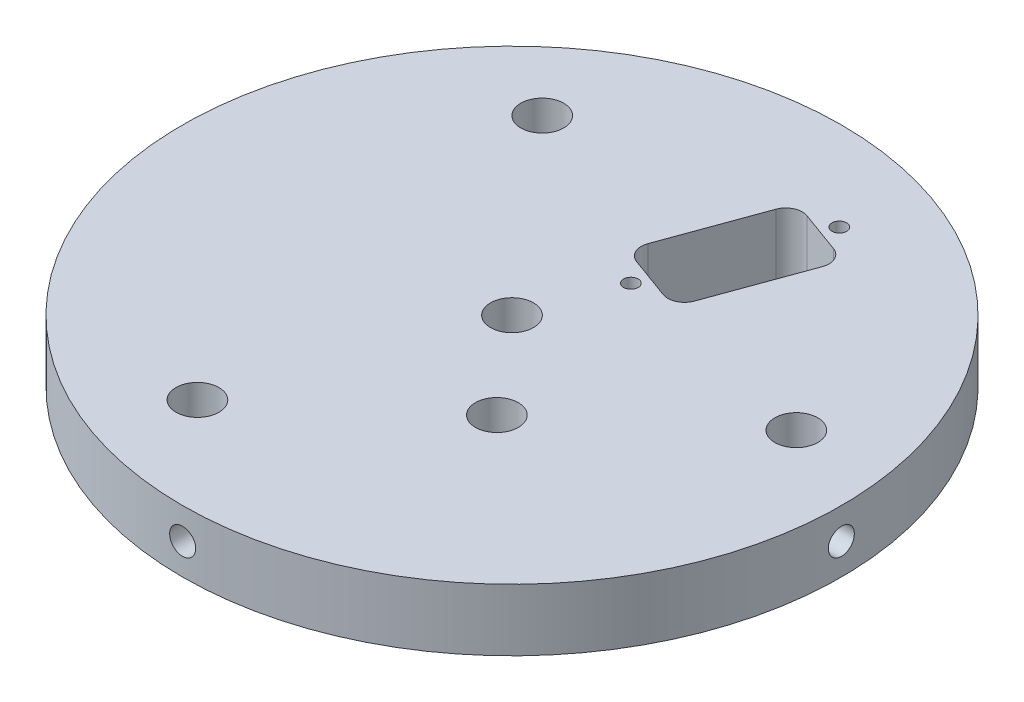
SolidWorks part; units mm, degrees
material "6061-T6 (SS)"
ref_plane "Front Plane" through (0, 0, 0) normal (0, 0, 1) x (1, 0, 0)
ref_plane "Top Plane" through (0, 0, 0) normal (0, 1, 0) x (1, 0, 0)
ref_plane "Right Plane" through (0, 0, 0) normal (1, 0, 0) x (0, 0, -1)
sketch "Sketch1" plane through (0, 0, 0) normal (0, 1, 0) x (1, 0, 0)
  line L0 (0, 0) -> (-50.3682, 60.0265)
  line L1 (0, 0) -> (50.3682, 60.0265)
  line L2 (0, 0) -> (0, 72.1431) construction
  circle A0 centre (0, 0) radius 78.359
  circle A1 centre (0, 0) radius 76.1746
  circle A2 centre (0, 0) radius 76.1746
  dimension "D1" = 156.718
  dimension "D2" = 152.3492
  dimension "D3" = 152.3492
  dimension "D4" = 80
extrude "Boss-Extrude1" add sketch "Sketch1" along normal blind 25.4 contours L2 A2 L1 A0 | L2 A1 L1 A2 | L2 A2 L1 A1 | L2 A0 L1 A2 | A2 L2 A1 L0 | A0 L2 A2 L0 | A2 L2 A0 L0 | A1 L2 A2 L0 region at (0, 0, 13.3592) region at (-23.5316, 0, -29.974) region at (-33.0764, 0, 70.9325) region at (-48.8794, 0, -59.85)
ref_plane "Plane1" through (0, 12.7, 0) normal (0, 1, 0) x (1, 0, 0)
sketch "Sketch6" plane through (0, 25.4, 0) normal (0, 1, 0) x (1, 0, 0)
  circle A0 centre (0, 0) radius 76.1746
  dimension "D1" = 152.3492
extrude "Boss-Extrude5" add sketch "Sketch6" along normal blind 9.525
sketch "Sketch7" plane through (0, 0, 0) normal (0, -1, 0) x (1, 0, 0)
  circle A0 centre (0, 0) radius 76.1746
  dimension "D1" = 152.3492
extrude "Boss-Extrude6" add sketch "Sketch7" along normal blind 9.525
sketch "Sketch8" plane through (0, -9.525, 0) normal (0, -1, 0) x (1, 0, 0)
  circle A0 centre (0, 0) radius 73.025
  dimension "D1" = 146.05
extrude "Cut-Extrude5" cut sketch "Sketch8" against normal up to surface (34.925 mm away) up to face at (0, 25.4, 76.1746)
ref_plane "Plane2" through (0, 0, -76.1746) normal (0, 0, -1) x (-1, 0, 0)
ref_plane "Plane5" through (0, 25.4, 0) normal (0, 1, 0) x (1, 0, 0)
ref_axis "Axis1" through (0, 0, 0) along (0, 1, 0)
sketch "Sketch3" plane through (0, 0, -76.1746) normal (0, 0, -1) x (-1, 0, 0)
  line L4 (76.1746, 0) -> (-76.1746, 0)
  line L5 (-76.1746, -9.525) -> (76.1746, -9.525)
  line L6 (76.1746, 25.4) -> (-76.1746, 25.4)
  line L7 (76.1746, 34.925) -> (-76.1746, 34.925)
  line L8 (0, 34.925) -> (0, 25.4) construction
  line L9 (0, 0) -> (0, -9.525) construction
  circle A0 centre (0, 30.1625) radius 2
  circle A1 centre (0, -4.7625) radius 2
  point P12 (0, 30.1625)
  point P13 (0, -4.7625)
  point P14 (-77.5445, 179.1871)
  dimension "D1" = 4
extrude "Cut-Extrude2" cut sketch "Sketch3" against normal blind 34.925 contours L8 A0 | L8 A0 | L9 A1 | L9 A1 region at (-0.8488, 30.1625, -76.1746) region at (0.8488, 30.1625, -76.1746) region at (-0.8488, -4.7625, -76.1746) region at (0.8488, -4.7625, -76.1746)
extrude "Cut-Extrude3" cut sketch "Sketch1<7>" against normal blind 9.525 from surface contours L2 A1 L1 A2 | A1 L2 A2 L0 | A2 L2 A0 L0 | L2 A2 L1 A0 region at (-23.5316, 0, -29.974) region at (-48.8794, 0, -59.85) starting at plane "Plane5"
sketch "Sketch1<7>" plane through (0, 0, 0) normal (0, 1, 0) x (1, 0, 0) same geometry as "Sketch1"
pattern_circular "CirPattern2" count 3 over 360 about axis through (0, 0, 0) along (0, 1, 0) of "Cut-Extrude3"
ref_plane "Plane3" through (0, 34.925, 0) normal (0, 1, 0) x (1, 0, 0)
sketch "Sketch4" plane through (0, 34.925, 0) normal (0, 1, 0) x (1, 0, 0)
  circle A0 centre (0, 0) radius 73.025
  dimension "D1" = 146.05
extrude "Boss-Extrude4" add sketch "Sketch4" against normal blind 9.525
pattern_circular "CirPattern3" count 4 over 360 about axis through (0, 0, 0) along (0, 1, 0) of "Cut-Extrude2"
sketch "Sketch9" plane through (0, 34.925, 0) normal (0, 1, 0) x (1, 0, 0)
  line L0 (0, 0) -> (-26.8004, -73.6334) construction
  line L1 (0, 0) -> (24.0447, -28.6554) construction
  circle A0 centre (0, 0) radius 3.3
  circle A1 centre (-12.9007, -35.4443) radius 3.3
  circle A2 centre (-24.2453, 28.8944) radius 3.3
  circle A3 centre (37.146, 6.5498) radius 3.3
  circle A4 centre (12.1227, -14.4472) radius 3.3
  point P15 (0, 0)
  dimension "D1" = 6.6
  dimension "D2" = 6.6
  dimension "D6" = 6.6
  dimension "D3" = 37.719
  dimension "D4" = 60
  dimension "D7" = 18.8595
  dimension "D5" = 3
extrude "Cut-Extrude6" cut sketch "Sketch9" against normal through all
sketch "Sketch10" plane through (0, 25.4, 0) normal (0, 1, 0) x (1, 0, 0)
  circle A0 centre (0, 0) radius 82.3228
extrude "Cut-Extrude7" cut sketch "Sketch10" against normal through all
hole_wizard "Tap Drill for #4-40 Tap1" positions "Sketch12" profile "Sketch13" hole size "#4-40" standard "ANSI Inch" end condition through all
sketch "Sketch12" plane through (0, 34.925, 0) normal (0, 1, 0) x (1, 0, 0)
  line L0 (0, 0) -> (18.6243, 51.1699) construction
  line L2 (0, 0) -> (-24.2453, 28.8944) construction
  circle A0 centre (0, 0) radius 14.2494 construction
  point P0 (4.8736, 13.3901)
  point P2 (13.4241, 36.8824)
  dimension "D3" = 28.4988
  dimension "D1" = 60
  dimension "D2" = 25
sketch "Sketch13" plane through (4.8736, 34.925, -13.3901) normal (1, 0, 0) x (0, 0, 1)
  line L0 (0, 0) -> (0, 9.525)
  line L1 (0, 9.525) -> (1.1303, 9.525)
  line L2 (1.1303, 9.525) -> (1.1303, 0)
  line L5 (1.1303, 0) -> (0, 0)
  line L11 (0, -6.35) -> (0, 107.95) construction
  dimension "Thru Hole Dia." = 2.2606
  dimension "Thru Hole Depth" = 9.525
sketch "Sketch14" plane through (0, 34.925, 0) normal (0, 1, 0) x (1, 0, 0)
  line L0 (4.8736, 13.3901) -> (13.4241, 36.8824) construction
  line L1 (12.1332, 15.8835) -> (17.3825, 30.3059)
  line L2 (8.8776, 14.3654) -> (2.4332, 16.711)
  line L3 (15.8644, 33.5614) -> (9.42, 35.907)
  line L4 (0.9151, 19.9665) -> (6.1645, 34.3889)
  arc A0 (17.3825, 30.3059) -> (15.8644, 33.5614) centre (14.9957, 31.1746) ccw
  arc A1 (9.42, 35.907) -> (6.1645, 34.3889) centre (8.5513, 33.5202) ccw
  arc A2 (8.8776, 14.3654) -> (12.1332, 15.8835) centre (9.7464, 16.7522) ccw
  arc A3 (2.4332, 16.711) -> (0.9151, 19.9665) centre (3.302, 19.0978) cw
  point P0 (5.6554, 15.5382)
  point P17 (0, 0)
  point P18 (15.9347, 43.7803)
  dimension "D4" = 2.54
  dimension "D5" = 2.54
  dimension "D1" = 2.286
  dimension "D2" = 2.286
  dimension "D3" = 11.938
extrude "Cut-Extrude9" cut sketch "Sketch14" against normal through all
sketch "Sketch15" plane through (0, 34.925, 0) normal (0, 1, 0) x (1, 0, 0)
  circle A0 centre (0, 0) radius 50.6476
  circle A1 centre (0, 0) radius 88.636
  dimension "D1" = 101.2952
extrude "Cut-Extrude10" cut sketch "Sketch15" against normal up to next
pattern_circular "CirPattern4" count 4 over 360 about axis through (0, -9.525, 0) along (0, 1, 0) of "CirPattern3" reverse direction yes
equation "\"AB_Coupler_OD_Length\"= 1in"
equation "\"AB_Coupling_Section_Length\"= 0.375in"
equation "\"AB_Coupler_Length\"= \"AB_Coupler_OD_Length\" + \"AB_Coupling_Section_Length\" * 2"
equation "\"Cutout_Angle\" = 80"
equation "\"AB_Coupler_Num_Screws\"= 6"
equation "\"Num_Cutouts\" = 3"
equation "\"AB_Coupler_OD\"= 6.17in"
equation "\"AB_Coupler_ID\"= 5.75in"
equation "\"AB_Coupler_Surface_Diameter\"= 5.998in"
equation "\"D2@Sketch1\"=\"Bodytube_ID\""
equation "\"AB_Coupling_Screw_Diameter\"= 0.1065in"
equation "\"Aft_Section_Length\"= 39in"
equation "\"Aft_Lower_Length\"= 22in"
equation "\"Aft_Upper_Length\"= \"Aft_Section_Length\" - \"Aft_Lower_Length\" - \"AB_Coupler_OD_Length\""
equation "\"Mid_Coupler_Length\"= 13in"
equation "\"Lead_Screw_Dist\" = 2.25in"
equation "\"Lead_Screw_Diam\" = 11mm"
equation "\"Lead_Screw_Length\" = (\"Mid_Coupler_Length\" + 2*0.375in + 2*0.5in)"
equation "\"Bodytube_OD\" = 6.17in"
equation "\"Paddle_Pin_Offset\" = .25in"
equation "\"Bodytube_ID\" = 5.998in"
equation "\"Paddle_Pin_Radius\" = 2.25in"
equation "\"D1@Sketch4\"=\"AB_Coupler_ID\""
equation "\"D1@Sketch6\"=\"AB_Coupler_Surface_Diameter\""
equation "\"D1@Boss-Extrude5\"=\"AB_Coupling_Section_Length\""
equation "\"D1@Sketch7\"=\"AB_Coupler_Surface_Diameter\""
equation "\"D1@Boss-Extrude6\"=\"AB_Coupling_Section_Length\""
equation "\"D1@Sketch8\"=\"AB_Coupler_ID\""
equation "\"D3@Sketch9\"=\"Paddle_Pin_Radius\"*.66"
equation "\"Motor_OD\" = 4in"
equation "\"Fwd_Tube_Length\" = 40in"
equation "\"Mid_Tube_Length\" = 1in"
equation "\"AB_Paddle_Height\" = 0.375in"
equation "\"AB_Central_Bushing_Length\" = .75in"
equation "\"Paddle_Gear_OD\" = 3.2in"
equation "\"Fwd_BKHD_From_Top\" = 18in"
equation "\"Fin_Thickness\"= .118in"
equation "\"Guiderail_Cutout_Diameter\"= 1.5in"
equation "\"DB9_Hole_Dist\" = 25mm"
equation "\"D2@Sketch12\"=\"DB9_Hole_Dist\""
equation "\"Drive_Gear_OD\" = 1.7in"
equation "\"D3@Sketch12\"=\"Drive_Gear_OD\"*0.66"
